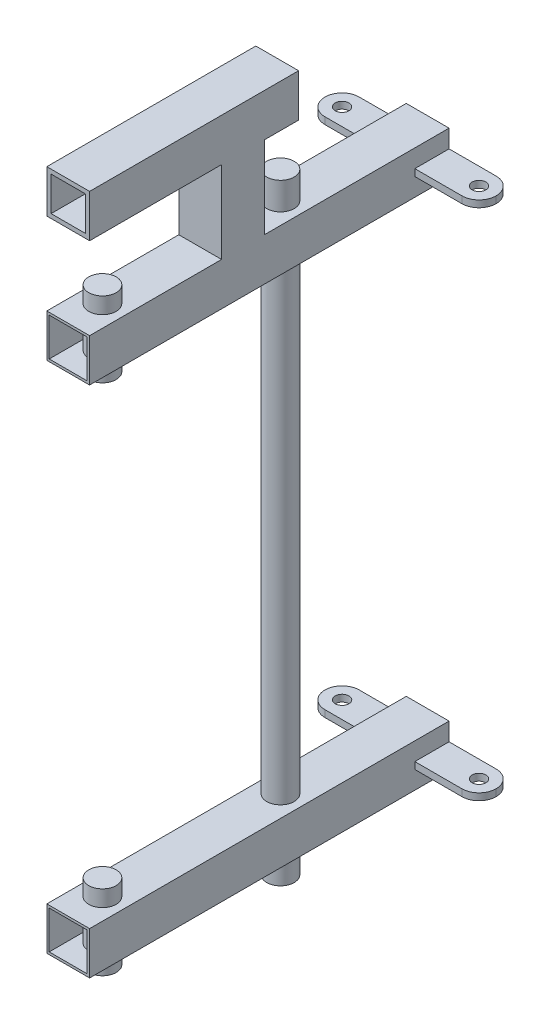
SolidWorks part; units mm, degrees
ref_plane "Front Plane" through (0, 0, 0) normal (0, 0, 1) x (1, 0, 0)
ref_plane "Top Plane" through (0, 0, 0) normal (0, 1, 0) x (1, 0, 0)
ref_plane "Right Plane" through (0, 0, 0) normal (1, 0, 0) x (0, 0, -1)
sketch "Sketch2" plane through (0, 0, 0) normal (0, 0, 1) x (1, 0, 0)
  line L0 (5.55, 5.55) -> (-5.55, 5.55)
  line L1 (6.25, -6.25) -> (-6.25, -6.25)
  line L2 (6.25, -6.25) -> (6.25, 6.25)
  line L3 (6.25, 6.25) -> (-6.25, 6.25)
  line L4 (-6.25, -6.25) -> (-6.25, 6.25)
  line L5 (6.25, -6.25) -> (-6.25, 6.25) construction
  line L6 (6.25, 6.25) -> (-6.25, -6.25) construction
  line L7 (-5.55, -5.55) -> (-5.55, 5.55)
  line L8 (5.55, -5.55) -> (-5.55, -5.55)
  line L9 (5.55, -5.55) -> (5.55, 5.55)
  point P0 (0, 0)
  dimension "D1" = 12.5
  dimension "D2" = 12.5
  dimension "D3" = 0.7
extrude "Boss-Extrude1" add sketch "Sketch2" along normal blind 105
sketch "Sketch3" plane through (0, 6.25, 0) normal (0, 1, 0) x (1, 0, 0)
  line L0 (6.25, -105) -> (-6.25, -105) construction
  circle A0 centre (0, -95) radius 4
  dimension "D1" = 10
extrude "Cut-Extrude1" cut sketch "Sketch3" against normal blind 105
ref_plane "Plane1" through (0, 0, 0) normal (1, 0, 0) x (0, 0, -1)
sketch "Sketch4" plane through (0, 0, 0) normal (1, 0, 0) x (0, 0, -1)
  line L0 (0, 1) -> (0, -1)
  line L1 (0, -1) -> (-10, -1)
  line L3 (0, 1) -> (-10, 1)
  line L4 (-10, -1) -> (-10, 1)
  dimension "D1" = 10
  dimension "D2" = 2
extrude "Boss-Extrude2" add sketch "Sketch4" along normal mid plane 50
fillet "Fillet1" radius 5 4 edges at (-25, 0, 10) (-25, 0, 0) (25, 0, 10) (25, 0, 0)
sketch "Sketch5" plane through (0, 1, 0) normal (0, 1, 0) x (1, 0, 0)
  circle A0 centre (20, -5) radius 2
extrude "Cut-Extrude2" cut sketch "Sketch5" against normal blind 40
mirror "Mirror1" about plane through (0, 0, 0) normal (1, 0, 0) of "Cut-Extrude2"
ref_plane "Plane2" through (0, -75, 0) normal (0, -1, 0) x (-1, 0, 0)
mirror "Mirror3" about plane through (0, -75, 0) normal (0, -1, 0) of bodies 105
sketch "Sketch6" plane through (0, 6.25, 0) normal (0, 1, 0) x (1, 0, 0)
  line L0 (0, -6.875) -> (0, 6.875) construction
  line L1 (6.25, 0) -> (-6.25, 0) construction
  circle A0 centre (0, -43) radius 4
  dimension "D1" = 43
extrude "Boss-Extrude3" add sketch "Sketch6" along normal blind 8 and the other way blind 82.5
mirror "Mirror4" about plane through (0, -75, 0) normal (0, -1, 0) of "Boss-Extrude3"
sketch "Sketch8" plane through (0, 6.25, 0) normal (0, 1, 0) x (1, 0, 0)
  line L0 (0, -6.875) -> (0, 6.875) construction
  line L1 (-6.25, -66.4504) -> (6.25, -66.4504)
  line L2 (-6.25, -66.4504) -> (-6.25, -53.9504)
  line L3 (-6.25, -53.9504) -> (6.25, -53.9504)
  line L4 (6.25, -66.4504) -> (6.25, -53.9504)
  line L5 (-6.25, -66.4504) -> (6.25, -53.9504) construction
  line L6 (-6.25, -53.9504) -> (6.25, -66.4504) construction
  line L7 (6.25, -105) -> (6.25, 0) construction
  line L8 (-5.55, -54.6504) -> (5.55, -54.6504)
  line L9 (5.55, -65.7504) -> (5.55, -54.6504)
  line L10 (-5.55, -65.7504) -> (5.55, -65.7504)
  line L11 (-5.55, -65.7504) -> (-5.55, -54.6504)
  point P0 (0, -60.2004)
  dimension "D1" = 12.5
  dimension "D2" = 0.7
extrude "Boss-Extrude4" add sketch "Sketch8" along normal blind 24
sketch "Sketch9" plane through (0, 0, 53.9504) normal (0, 0, -1) x (-1, 0, 0)
  line L0 (0, 6.875) -> (0, -6.875) construction
  line L1 (-6.25, 42.75) -> (6.25, 42.75)
  line L2 (-6.25, 42.75) -> (-6.25, 30.25)
  line L3 (-6.25, 30.25) -> (6.25, 30.25)
  line L4 (6.25, 42.75) -> (6.25, 30.25)
  line L5 (-6.25, 42.75) -> (6.25, 30.25) construction
  line L6 (-6.25, 30.25) -> (6.25, 42.75) construction
  line L7 (-5, 41.5) -> (5, 41.5)
  line L8 (5, 41.5) -> (5, 31.5)
  line L9 (-5, 31.5) -> (5, 31.5)
  line L10 (-5, 41.5) -> (-5, 31.5)
  point P0 (0, 36.5)
  dimension "D1" = 12.5
  dimension "D2" = 1.25
extrude "Boss-Extrude5" add sketch "Sketch9" along normal blind 10 and the other way up to vertex (51.0496 mm away) other way up to point (6.25, 6.25, 105)
ref_plane "Plane3" through (0, 0, 0) normal (0, 1, 0) x (1, 0, 0)
sketch "Sketch11" plane through (0, 0, 0) normal (0, 1, 0) x (1, 0, 0)
  circle A0 centre (0, -95) radius 4
extrude "Boss-Extrude6" add sketch "Sketch11" along normal mid plane 22
ref_plane "Plane4" through (0, -150, 0) normal (0, -1, 0) x (-1, 0, 0)
sketch "Sketch12" plane through (0, -150, 0) normal (0, -1, 0) x (-1, 0, 0)
  circle A0 centre (0, -95) radius 4
extrude "Boss-Extrude7" add sketch "Sketch12" along normal mid plane 22
sketch "Sketch13" plane through (0, 0, 105) normal (0, 0, 1) x (1, 0, 0)
  line L1 (-5, 31.5) -> (5, 31.5)
  line L2 (-5, 31.5) -> (-5, 41.5)
  line L3 (-5, 41.5) -> (5, 41.5)
  line L4 (5, 31.5) -> (5, 41.5)
extrude "Boss-Extrude8" [suppressed] add sketch "Sketch13" along normal blind 22 and the other way blind 19
sketch "Sketch15" [suppressed] plane through (0, 0, 0) normal (1, 0, 0) x (0, 0, -1)
  line L0 (-127, 41.5) -> (-127, 31.5) construction
  circle A0 centre (-125, 36.5) radius 2
  dimension "D1" = 2
extrude "Boss-Extrude9" [suppressed] add sketch "Sketch15" along normal mid plane 60
